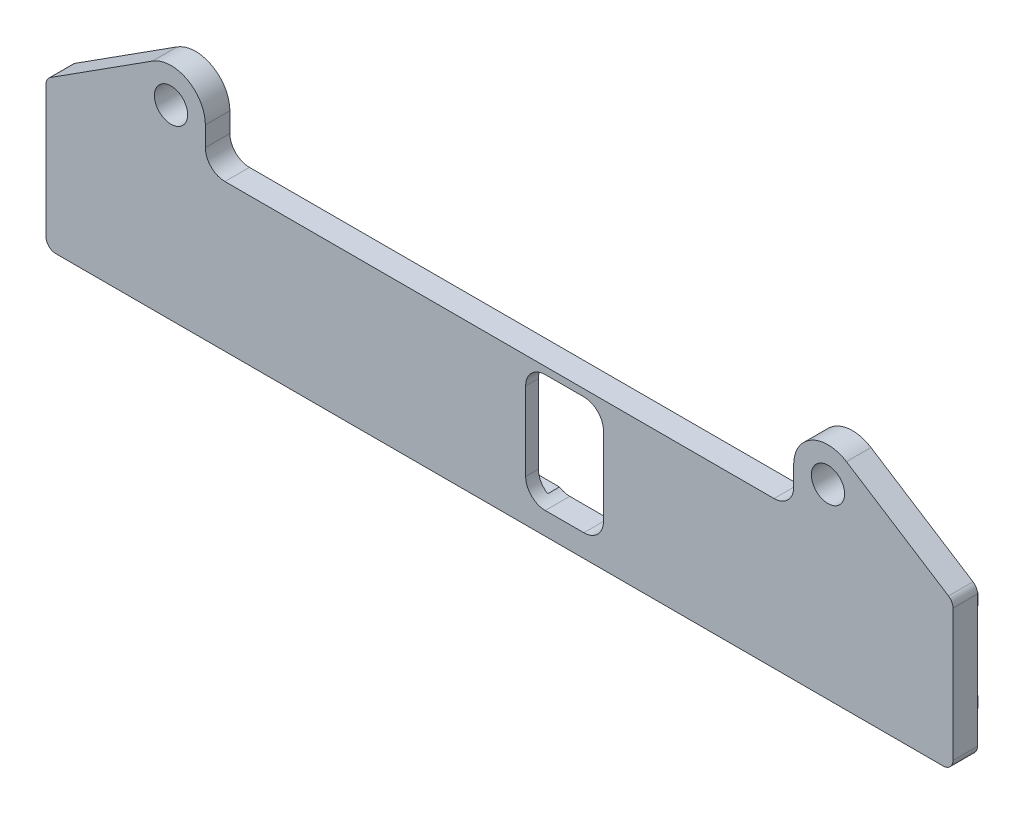
SolidWorks part; units mm, degrees
material "ABS PC"
ref_plane "Front Plane" through (0, 0, 0) normal (0, 0, 1) x (1, 0, 0)
ref_plane "Top Plane" through (0, 0, 0) normal (0, 1, 0) x (1, 0, 0)
ref_plane "Right Plane" through (0, 0, 0) normal (1, 0, 0) x (0, 0, -1)
sketch "Sketch1" plane through (0, 0, 0) normal (0, 0, 1) x (1, 0, 0)
  line L16 (58.7375, -67.1355) -> (58.7375, -48.0855)
  line L17 (58.7375, -48.0855) -> (44.94, -39.2609)
  line L18 (38.1, -43.0055) -> (38.1, -45.5455)
  line L19 (35.56, -48.0855) -> (-35.56, -48.0855)
  line L20 (-38.1, -45.5455) -> (-38.1, -43.0055)
  line L21 (-44.94, -39.2609) -> (-58.7375, -48.0855)
  line L22 (-58.7375, -48.0855) -> (-58.7375, -67.1355)
  line L23 (-58.7375, -67.1355) -> (58.7375, -67.1355)
  arc A8 (44.94, -39.2609) -> (38.1, -43.0055) centre (42.545, -43.0055) ccw
  arc A9 (35.56, -48.0855) -> (38.1, -45.5455) centre (35.56, -45.5455) ccw
  arc A10 (-38.1, -45.5455) -> (-35.56, -48.0855) centre (-35.56, -45.5455) ccw
  arc A11 (-38.1, -43.0055) -> (-44.94, -39.2609) centre (-42.545, -43.0055) ccw
extrude "Boss-Extrude1" add sketch "Sketch1" along normal blind 3.175
hole_wizard "#6 Clearance Hole1" positions "Sketch3" profile "Sketch2" hole size "#6" standard "ANSI Inch" end condition through all
sketch "Sketch3" plane through (0, 0, 0) normal (0, 0, -1) x (-1, 0, 0)
  point P0 (42.545, -43.0055)
  point P3 (-42.545, -43.0055)
sketch "Sketch2" plane through (-42.545, -43.0055, 0) normal (1, 0, 0) x (0, 1, 0)
  line L0 (0, 0) -> (0, 3.175)
  line L1 (0, 3.175) -> (2.1526, 3.175)
  line L2 (2.1526, 3.175) -> (2.1526, 0)
  line L5 (2.1526, 0) -> (0, 0)
  line L11 (0, -6.35) -> (0, 107.95) construction
  dimension "Thru Hole Dia." = 4.3053
  dimension "Thru Hole Depth" = 3.175
fillet "Fillet3" radius 1.27 4 edges at (58.7375, -67.1355, 1.5875) (58.7375, -48.0855, 1.5875) (-58.7375, -48.0855, 1.5875) (-58.7375, -67.1355, 1.5875)
sketch "Sketch4" plane through (0, 0, 3.175) normal (0, 0, 1) x (1, 0, 0)
  line L0 (10.4267, -56.6199) -> (6.4267, -56.6199) construction
  line L1 (13.4667, -64.2399) -> (3.3867, -64.2399)
  line L2 (13.4667, -64.2399) -> (13.4667, -48.9999)
  line L3 (13.4667, -48.9999) -> (3.3867, -48.9999)
  line L4 (3.3867, -64.2399) -> (3.3867, -48.9999)
  line L5 (13.4667, -64.2399) -> (3.3867, -48.9999) construction
  line L6 (13.4667, -48.9999) -> (3.3867, -64.2399) construction
  line L7 (5.9267, -52.0399) -> (5.9267, -53.5799) construction
  line L8 (10.4267, -51.5399) -> (6.4267, -51.5399) construction
  point P0 (8.4267, -56.6199)
  dimension "D1" = 2.54
  dimension "D2" = 2.54
extrude "Cut-Extrude1" cut sketch "Sketch4" against normal through all
fillet "Fillet4" radius 2.54 4 edges at (3.3867, -64.2399, 1.5875) (13.4667, -64.2399, 1.5875) (13.4667, -48.9999, 1.5875) (3.3867, -48.9999, 1.5875)
sketch "Sketch7" plane through (0, 0, 0) normal (0, 0, -1) x (-1, 0, 0)
  line L0 (58.039, -60.8725) -> (58.039, -52.3672)
  line L1 (58.039, -52.3672) -> (55.0526, -49.3809)
  line L2 (55.0526, -49.3809) -> (-55.0526, -49.3809)
  line L3 (-55.0526, -49.3809) -> (-58.039, -52.3672)
  line L4 (-58.039, -52.3672) -> (-58.039, -60.8725)
  line L5 (-58.039, -60.8725) -> (-55.0526, -63.8589)
  line L6 (-55.0526, -63.8589) -> (55.0526, -63.8589)
  line L7 (55.0526, -63.8589) -> (58.039, -60.8725)
  line L8 (57.277, -60.5569) -> (57.277, -52.6829)
  line L9 (57.277, -52.6829) -> (54.737, -50.1429)
  line L10 (54.737, -50.1429) -> (-54.737, -50.1429)
  line L11 (-54.737, -50.1429) -> (-57.277, -52.6829)
  line L12 (-57.277, -52.6829) -> (-57.277, -60.5569)
  line L13 (-57.277, -60.5569) -> (-54.737, -63.0969)
  line L14 (-54.737, -63.0969) -> (54.737, -63.0969)
  line L15 (54.737, -63.0969) -> (57.277, -60.5569)
  line L16 (57.277, -60.5569) -> (57.277, -52.6829) construction
  line L17 (57.277, -52.6829) -> (54.737, -50.1429) construction
  line L18 (54.737, -50.1429) -> (-54.737, -50.1429) construction
  line L19 (-54.737, -50.1429) -> (-57.277, -52.6829) construction
  line L20 (-57.277, -52.6829) -> (-57.277, -60.5569) construction
  line L21 (-57.277, -60.5569) -> (-54.737, -63.0969) construction
  line L22 (-54.737, -63.0969) -> (54.737, -63.0969) construction
  line L23 (54.737, -63.0969) -> (57.277, -60.5569) construction
  dimension "D1" = 0
  dimension "D2" = 0.762
extrude "Cut-Extrude2" cut sketch "Sketch7" against normal blind 1.524
sketch "Sketch5" plane through (0, 0, 0) normal (0, 0, -1) x (-1, 0, 0)
  line L0 (-57.277, -52.6829) -> (-54.737, -50.1429) construction
  line L1 (-55.8146, -50.1429) -> (-57.277, -50.1429)
  line L2 (-57.277, -50.1429) -> (-57.277, -51.6052)
  line L3 (-57.277, -60.5569) -> (-54.737, -63.0969) construction
  line L4 (-57.277, -60.5569) -> (-54.737, -63.0969) construction
  line L5 (-55.8146, -63.0969) -> (-57.277, -63.0969)
  line L6 (-57.277, -63.0969) -> (-57.277, -61.6345)
  line L7 (54.737, -63.0969) -> (57.277, -60.5569) construction
  line L8 (57.277, -61.6345) -> (57.277, -63.0969)
  line L9 (57.277, -63.0969) -> (55.8146, -63.0969)
  line L10 (57.277, -52.6829) -> (54.737, -50.1429) construction
  line L11 (-54.737, -50.1429) -> (54.737, -50.1429) construction
  line L12 (55.8146, -50.1429) -> (57.277, -50.1429)
  line L13 (57.277, -50.1429) -> (57.277, -51.6052)
  line L14 (-57.277, -51.6052) -> (-55.8146, -50.1429)
  line L15 (-57.277, -61.6345) -> (-55.8146, -63.0969)
  line L16 (55.8146, -63.0969) -> (57.277, -61.6345)
  line L17 (57.277, -51.6052) -> (55.8146, -50.1429)
  line L18 (57.8158, -52.1441) -> (55.2758, -49.6041) construction
  line L19 (55.2758, -63.6357) -> (57.8158, -61.0957) construction
  line L20 (-57.8158, -61.0957) -> (-55.2758, -63.6357) construction
  line L21 (-57.8158, -52.1441) -> (-55.2758, -49.6041) construction
  dimension "D1" = 0.762
  dimension "D2" = 0.762
extrude "Boss-Extrude2" add sketch "Sketch5" along normal blind 1.524
